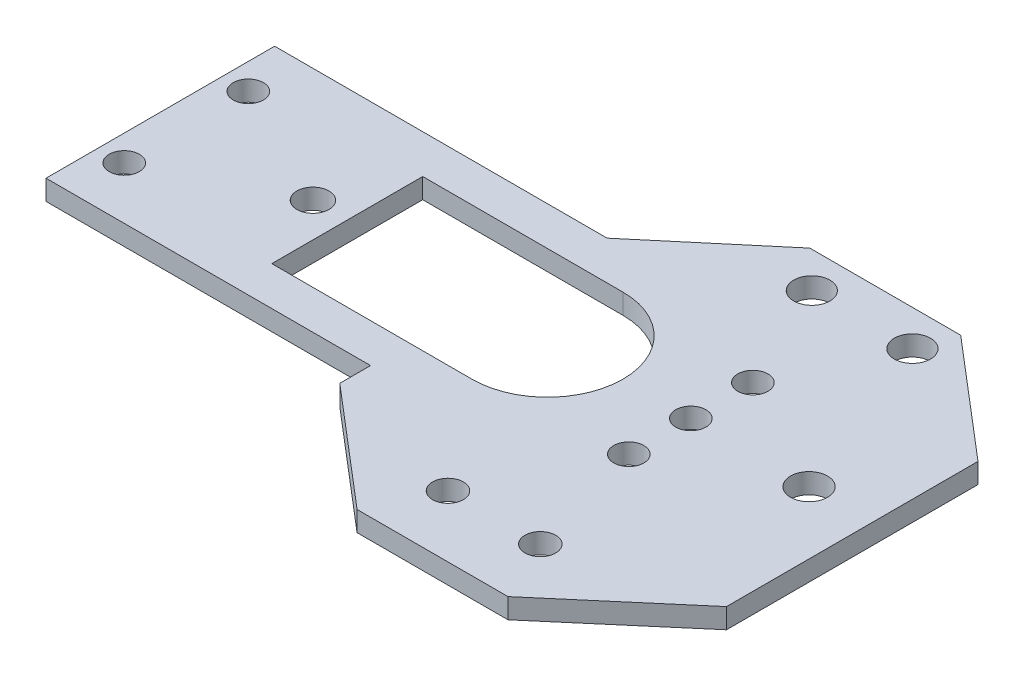
SolidWorks part; units mm, degrees
ref_plane "Alzado" through (0, 0, 0) normal (0, 0, 1) x (1, 0, 0)
ref_plane "Planta" through (0, 0, 0) normal (0, 1, 0) x (1, 0, 0)
ref_plane "Vista lateral" through (0, 0, 0) normal (1, 0, 0) x (0, 0, -1)
sketch "Croquis1" plane through (0, 0, 0) normal (0, 1, 0) x (1, 0, 0)
  line L0 (-26.5149, -10.5826) -> (-26.5149, -7.5272)
  line L1 (-14.7949, 24.4174) -> (0.2051, 24.4174)
  line L2 (-26.5149, -10.5826) -> (-14.7949, -20.5826)
  line L3 (-14.7949, -20.5826) -> (0.2051, -20.5826)
  line L4 (11.9251, 14.4174) -> (11.9251, -10.5826)
  line L5 (-7.2949, -20.5826) -> (-7.2949, 24.4174) construction
  line L6 (-26.5149, -7.5272) -> (-40.887, -7.5272)
  line L7 (11.9251, -10.5826) -> (0.2051, -20.5826)
  line L8 (-25.725, 15.2001) -> (-14.7949, 24.4174)
  line L9 (0.2051, 24.4174) -> (11.9251, 14.4174)
  line L10 (-14.7949, -20.5826) -> (-14.7949, 24.4174) construction
  line L11 (0.2051, -20.5826) -> (0.2051, 24.4174) construction
  line L12 (-14.7949, -2.3239) -> (0.2051, -2.3239) construction
  line L13 (11.9251, -10.5826) -> (-26.5149, -10.5826) construction
  line L14 (11.9251, 14.4174) -> (-27.2565, 14.4174) construction
  line L15 (-41.4058, 15.2001) -> (-25.725, 15.2001)
  line L16 (-11.8849, -14.4576) -> (-2.7049, -14.4576) construction
  line L17 (-20.2949, 3.8424) -> (5.7051, 3.8424) construction
  line L18 (-52.2565, 3.8424) -> (-52.2565, 28.8425) construction
  line L19 (-40.1956, 11.3424) -> (-20.2949, 11.3424)
  line L20 (-40.1956, 11.3424) -> (-40.1956, -3.6576)
  line L21 (-40.1956, -3.6576) -> (-20.2949, -3.6576)
  line L22 (-20.2949, 3.8424) -> (-52.2565, 3.8424) construction
  line L23 (-27.2565, 14.4174) -> (-27.2565, 26.4393) construction
  line L24 (-41.4058, 15.2001) -> (-58.7725, 15.2001)
  line L25 (-58.7725, 15.2001) -> (-58.7725, -7.5272)
  line L26 (-58.7725, -7.5272) -> (-40.887, -7.5272)
  line L27 (-6.0449, 10.0086) -> (-6.0449, -2.3239) construction
  line L28 (-14.7949, 10.0086) -> (0.2051, 10.0086) construction
  line L29 (-14.7949, 10.0086) -> (-58.7725, 10.0086) construction
  line L30 (-14.7949, -2.3239) -> (-58.7725, -2.3239) construction
  line L31 (-56.1949, 15.2001) -> (-56.1949, -7.5272) construction
  line L32 (-25.725, 15.2001) -> (-25.725, 14.4174) construction
  arc A0 (-41.4058, 15.2001) -> (-40.887, -7.5272) centre (-40.887, 3.8424) ccw construction
  circle A1 centre (-11.8849, -14.4576) radius 1.53
  circle A2 centre (-2.7049, -14.4576) radius 1.53
  arc A3 (-20.2949, -3.6576) -> (-20.2949, 11.3424) centre (-20.2949, 3.8424) ccw
  circle A4 centre (5.7051, 3.8424) radius 1.8379
  circle A5 centre (-43.6105, 3.8424) radius 1.5973
  circle A6 centre (-6.0449, 3.8424) radius 1.5
  circle A7 centre (-6.0449, 10.0086) radius 1.5
  circle A8 centre (-6.0449, -2.3239) radius 1.5
  circle A9 centre (-20.2949, 3.8424) radius 7.5 construction
  circle A10 centre (-56.1949, 10.0086) radius 1.5
  circle A11 centre (-56.1949, -2.3239) radius 1.5
  point P0 (0, 0)
  point P16 (0, 0)
  dimension "D12" = 3
  dimension "D13" = 15
  dimension "D10" = 3.06
  dimension "D1" = 15
  dimension "D2" = 10
  dimension "D3" = 45
  dimension "D4" = 10
  dimension "D5" = 6.125
  dimension "D6" = 26
  dimension "D7" = 18.3
  dimension "D8" = 9.18
  dimension "D9" = 25
  dimension "D11" = 14.25
  dimension "D14" = 48.9
extrude "Saliente-Extruir1" add sketch "Croquis1" along normal blind 2
sketch "Croquis2" plane through (0, 2, 0) normal (0, 1, 0) x (1, 0, 0)
  line L0 (-13.6286, 20.8624) -> (0, 20.8624) construction
  circle A0 centre (-11.0392, 20.8624) radius 1.8
  circle A1 centre (-1.0392, 20.8624) radius 1.8
  dimension "D1" = 3.6
  dimension "D2" = 10
extrude "Cortar-Extruir1" cut sketch "Croquis2" against normal blind 10
